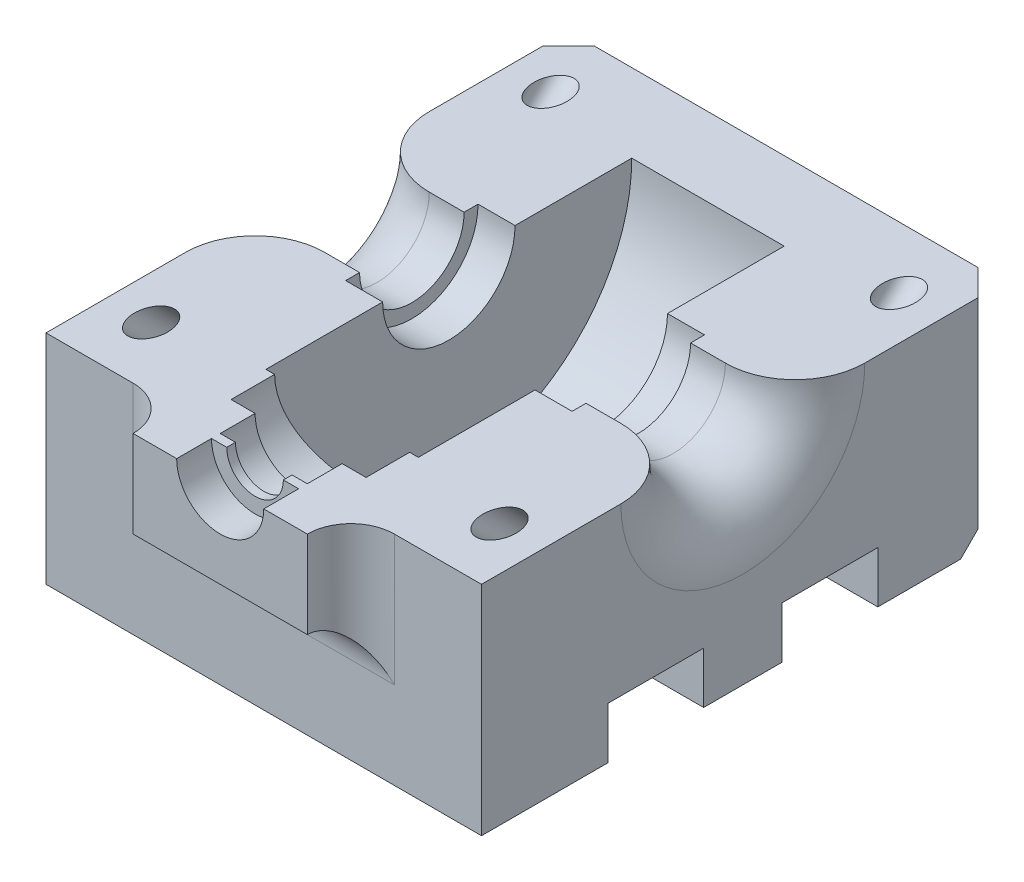
SolidWorks part; units mm, degrees
ref_plane "Front Plane" through (0, 0, 0) normal (0, 0, 1) x (1, 0, 0)
ref_plane "Top Plane" through (0, 0, 0) normal (0, 1, 0) x (1, 0, 0)
ref_plane "Right Plane" through (0, 0, 0) normal (1, 0, 0) x (0, 0, -1)
sketch "Sketch1" plane through (0, 0, 0) normal (0, 1, 0) x (1, 0, 0)
  line L1 (-25, 30) -> (25, 30)
  line L2 (-25, 30) -> (-25, -30)
  line L3 (-25, -30) -> (25, -30)
  line L4 (25, 30) -> (25, -30)
  line L5 (-25, 30) -> (25, -30) construction
  line L6 (-25, -30) -> (25, 30) construction
  point P0 (0, 0)
  dimension "D1" = 50
  dimension "D2" = 60
extrude "Boss-Extrude1" add sketch "Sketch1" along normal blind 25
sketch "Sketch2" plane through (-25, 0, 0) normal (-1, 0, 0) x (0, 0, 1)
  line L3 (-30, 25) -> (30, 25) construction
  line L6 (-30, 25) -> (-30, 0) construction
  circle A1 centre (0, 25) radius 21
  dimension "D1" = 42
  dimension "D2" = 9
extrude "Cut-Extrude1" cut sketch "Sketch2" against normal blind 17.5 from offset 16.25 offset against normal yes
sketch "Sketch3" plane through (-25, 0, 0) normal (-1, 0, 0) x (0, 0, 1)
  line L0 (-30, 25) -> (30, 25) construction
  line L1 (30, 25) -> (30, 0) construction
  circle A0 centre (0, 25) radius 7.6
  dimension "D1" = 15.2
  dimension "D2" = 30
extrude "Cut-Extrude2" cut sketch "Sketch3" against normal blind 26 from offset 12 offset against normal yes
sketch "Sketch4" plane through (0, 0, 30) normal (0, 0, 1) x (1, 0, 0)
  line L0 (-25, 25) -> (25, 25) construction
  circle A0 centre (0, 25) radius 5
  dimension "D1" = 10
extrude "Cut-Extrude3" cut sketch "Sketch4" against normal blind 4
sketch "Sketch5" plane through (0, 0, 0) normal (0, -1, 0) x (1, 0, 0)
  line L0 (-25, -30) -> (-25, 30) construction
  line L1 (25, -30) -> (-25, -30) construction
  circle A0 centre (-10, 20) radius 1.75
  circle A1 centre (10, 20) radius 1.75
  circle A2 centre (-10, -20) radius 1.75
  circle A3 centre (10, -20) radius 1.75
  dimension "D1" = 3.5
  dimension "D2" = 3.5
  dimension "D3" = 3.5
  dimension "D4" = 3.5
  dimension "D5" = 20
  dimension "D6" = 15
  dimension "D7" = 20
  dimension "D8" = 15
  dimension "D9" = 40
  dimension "D10" = 40
  dimension "D11" = 10
  dimension "D12" = 10
extrude "Cut-Extrude4" cut sketch "Sketch5" against normal blind 10
chamfer "Chamfer1" distance 5 angle 45 1 edges at (0, 0, -30)
sketch "Sketch6" plane through (0, 0, -30) normal (0, 0, -1) x (-1, 0, 0)
  line L0 (25, 25) -> (25, 5) construction
  line L1 (25, 0) -> (-25, 0) construction
  circle A0 centre (-20, 15) radius 1.75
  circle A1 centre (20, 15) radius 1.75
  dimension "D1" = 3.5
  dimension "D2" = 3.5
  dimension "D3" = 40
  dimension "D4" = 5
  dimension "D5" = 15
  dimension "D6" = 15
extrude "Cut-Extrude5" cut sketch "Sketch6" against normal blind 10
sketch "Sketch7" plane through (25, 0, 0) normal (1, 0, 0) x (0, 0, -1)
  line L0 (-30, 0) -> (25, 0) construction
  line L1 (-4.5, 0) -> (-15.5, 0)
  line L2 (-4.5, 0) -> (-4.5, 5.9067)
  line L3 (-4.5, 5.9067) -> (-15.5, 5.9067)
  line L4 (-15.5, 0) -> (-15.5, 5.9067)
  line L5 (30, 25) -> (30, 5) construction
  line L6 (15.5, 0) -> (4.5, 0)
  line L7 (15.5, 0) -> (15.5, 5.9067)
  line L8 (15.5, 5.9067) -> (4.5, 5.9067)
  line L9 (4.5, 0) -> (4.5, 5.9067)
  dimension "D1" = 14.5
  dimension "D2" = 11
  dimension "D3" = 9
  dimension "D4" = 11
extrude "Cut-Extrude6" cut sketch "Sketch7" against normal blind 9
chamfer "Chamfer2" distance 5 angle 45 2 edges at (16, 5.9067, -10) (16, 5.9067, 10)
mirror "Mirror1" about plane through (0, 0, 0) normal (1, 0, 0) of "Chamfer2", "Cut-Extrude6"
chamfer "Chamfer3" distance 3 angle 45 2 edges at (25, 15, -30) (-25, 15, -30)
ref_plane "Plane1" through (0, -2.5, -2.5) normal (0, 0.7071, 0.7071) x (1, 0, 0)
sketch "Sketch10" plane through (0, -2.5, -2.5) normal (0, 0.7071, 0.7071) x (1, 0, 0)
  line L0 (-25, 36.7696) -> (-25, -3.5355) construction
  line L1 (-25, -3.5355) -> (-5, -3.5355) construction
  circle A0 centre (-20, 1.4645) radius 1.9
  circle A1 centre (20, 1.4645) radius 1.9
  dimension "D1" = 3.8
  dimension "D3" = 3.8
  dimension "D2" = 40
  dimension "D4" = 5
  dimension "D5" = 5
extrude "Cut-Extrude8" cut sketch "Sketch10" along normal through all from offset 25
mirror "Mirror2" about plane through (0, 0, 0) normal (0, 0, 1) of "Cut-Extrude8"
sketch "Sketch12" plane through (-25, 0, 0) normal (-1, 0, 0) x (0, 0, 1)
  circle A0 centre (0, 25) radius 6
  dimension "D1" = 12
extrude "Cut-Extrude10" cut sketch "Sketch12" against normal through all both and the other way through all
fillet "Fillet1" radius 8 2 edges at (25, 19, 0)
sketch "Sketch16" plane through (0, 0, 26) normal (0, 0, 1) x (1, 0, 0)
  line L0 (8.75, 25) -> (-8.75, 25) construction
  circle A0 centre (0, 25) radius 7.75
  dimension "D1" = 15.5
extrude "Cut-Extrude13" cut sketch "Sketch16" against normal blind 8
sketch "Sketch17" plane through (0, 0, 30) normal (0, 0, 1) x (1, 0, 0)
  line L0 (-25, 25) -> (-5, 25) construction
  line L1 (-10, 25) -> (10, 25)
  line L2 (-10, 25) -> (-10, 15)
  line L3 (-10, 15) -> (10, 15)
  line L4 (10, 25) -> (10, 15)
  dimension "D1" = 5
  dimension "D2" = 5
  dimension "D3" = 10
extrude "Boss-Extrude2" add sketch "Sketch17" along normal blind 5
sketch "Sketch18" plane through (0, 0, 30) normal (0, 0, -1) x (-1, 0, 0)
  line L0 (-22, 25) -> (22, 25) construction
  circle A0 centre (0, 25) radius 3.25
  dimension "D1" = 6.5
extrude "Cut-Extrude14" cut sketch "Sketch18" against normal blind 10
sketch "Sketch19" plane through (0, 0, 35) normal (0, 0, 1) x (1, 0, 0)
  line L0 (8.75, 25) -> (-8.75, 25) construction
  circle A0 centre (0, 25) radius 5
  dimension "D1" = 10
extrude "Cut-Extrude15" cut sketch "Sketch19" against normal blind 4
fillet "Fillet2" radius 5 3 edges at (-10, 20, 30) (0, 15, 30) (10, 20, 30)
